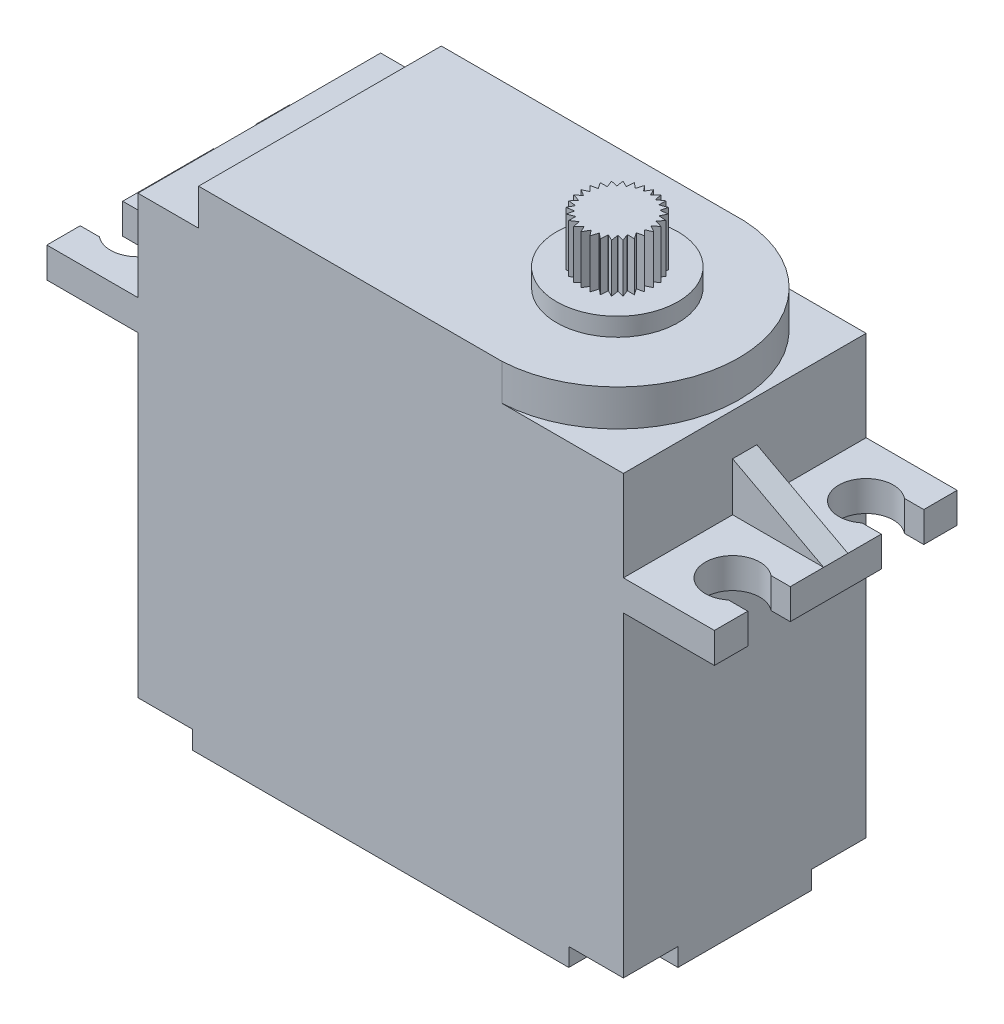
SolidWorks part; units mm, degrees
ref_plane "Front Plane" through (0, 0, 0) normal (0, 0, 1) x (1, 0, 0)
ref_plane "Top Plane" through (0, 0, 0) normal (0, 1, 0) x (1, 0, 0)
ref_plane "Right Plane" through (0, 0, 0) normal (1, 0, 0) x (0, 0, -1)
sketch "Sketch1" plane through (0, 0, 0) normal (0, 1, 0) x (1, 0, 0)
  line L1 (0, 0) -> (40, 0)
  line L2 (0, 0) -> (0, 20)
  line L3 (0, 20) -> (40, 20)
  line L4 (40, 0) -> (40, 20)
  dimension "D1" = 20
  dimension "D2" = 40
extrude "Boss-Extrude1" add sketch "Sketch1" along normal blind 40.5
sketch "Sketch2" plane through (0, 40.5, 0) normal (0, 1, 0) x (1, 0, 0)
  line L0 (40, 0) -> (40, 20) construction
  circle A0 centre (29.5, 10) radius 5
  dimension "D1" = 10.5
extrude "Boss-Extrude2" add sketch "Sketch2" along normal blind 1.5
sketch "Sketch3" plane through (40, 0, 0) normal (1, 0, 0) x (0, 0, -1)
  line L0 (0, 40.5) -> (0, 0) construction
  line L1 (0, 30.05) -> (20, 30.05)
  line L2 (0, 30.05) -> (0, 27.55)
  line L3 (0, 27.55) -> (20, 27.55)
  line L4 (20, 30.05) -> (20, 27.55)
  line L5 (20, 40.5) -> (20, 0) construction
  line L6 (0, 0) -> (20, 0) construction
  dimension "D1" = 27.55
  dimension "D2" = 2.5
extrude "Boss-Extrude3" add sketch "Sketch3" along normal blind 7.5
sketch "Sketch4" plane through (0, 0, 0) normal (-1, 0, 0) x (0, 0, 1)
  line L0 (-20, 40.5) -> (-20, 0) construction
  line L1 (-20, 30.05) -> (0, 30.05)
  line L2 (-20, 30.05) -> (-20, 27.55)
  line L3 (-20, 27.55) -> (0, 27.55)
  line L4 (0, 30.05) -> (0, 27.55)
  line L5 (0, 40.5) -> (0, 0) construction
  line L6 (-20, 0) -> (0, 0) construction
  dimension "D1" = 27.55
  dimension "D2" = 2.5
extrude "Boss-Extrude4" add sketch "Sketch4" along normal blind 7.5
sketch "Sketch5" plane through (0, 40.5, 0) normal (0, 1, 0) x (1, 0, 0)
  line L1 (40, 20) -> (0, 20) construction
  line L2 (5, 20) -> (5, 0)
  line L3 (0, 0) -> (40, 0) construction
  line L5 (5, 20) -> (0, 20)
  line L6 (0, 20) -> (0, 0)
  line L7 (0, 0) -> (5, 0)
  line L8 (30, 0) -> (40, 0)
  line L9 (40, 0) -> (40, 20)
  line L10 (40, 20) -> (30, 20)
  arc A3 (30, 0) -> (30, 20) centre (29.5, 10) ccw
extrude "Cut-Extrude1" cut sketch "Sketch5" against normal blind 3
sketch "Sketch6" plane through (0, 42, 0) normal (0, 1, 0) x (1, 0, 0)
  circle A0 centre (29.5, 10) radius 3
extrude "Boss-Extrude5" add sketch "Sketch6" along normal blind 4
sketch "Sketch7" plane through (0, 46, 0) normal (0, 1, 0) x (1, 0, 0)
  line L0 (29.5, 13) -> (29.1975, 12.4818)
  line L1 (29.5, 13) -> (29.7384, 12.4888)
  line L2 (30.1676, 12.9248) -> (29.7574, 12.4869)
  line L3 (30.1676, 12.9248) -> (30.2863, 12.3733)
  line L4 (30.8017, 12.7029) -> (30.3043, 12.3673)
  line L5 (30.8017, 12.7029) -> (30.7947, 12.1389)
  line L6 (31.3705, 12.3455) -> (30.8109, 12.1289)
  line L7 (31.3705, 12.3455) -> (31.2381, 11.7971)
  line L8 (31.8455, 11.8705) -> (31.2518, 11.7839)
  line L9 (31.8455, 11.8705) -> (31.5945, 11.3653)
  line L10 (32.2029, 11.3017) -> (31.6048, 11.3493)
  line L11 (32.2029, 11.3017) -> (31.8458, 10.865)
  line L12 (32.4248, 10.6676) -> (31.8523, 10.8471)
  line L13 (32.4248, 10.6676) -> (31.9794, 10.3213)
  line L14 (32.5, 10) -> (31.9818, 10.3025)
  line L15 (32.5, 10) -> (31.9888, 9.7616)
  line L16 (32.4248, 9.3324) -> (31.9869, 9.7426)
  line L17 (32.4248, 9.3324) -> (31.8733, 9.2137)
  line L18 (32.2029, 8.6983) -> (31.8673, 9.1957)
  line L19 (32.2029, 8.6983) -> (31.6389, 8.7053)
  line L20 (31.8455, 8.1295) -> (31.6289, 8.6891)
  line L21 (31.8455, 8.1295) -> (31.2971, 8.2619)
  line L22 (31.3705, 7.6545) -> (31.2839, 8.2482)
  line L23 (31.3705, 7.6545) -> (30.8653, 7.9055)
  line L24 (30.8017, 7.2971) -> (30.8493, 7.8952)
  line L25 (30.8017, 7.2971) -> (30.365, 7.6542)
  line L26 (30.1676, 7.0752) -> (30.3471, 7.6477)
  line L27 (30.1676, 7.0752) -> (29.8213, 7.5206)
  line L28 (29.5, 7) -> (29.8025, 7.5182)
  line L29 (29.5, 7) -> (29.2616, 7.5112)
  line L30 (28.8324, 7.0752) -> (29.2426, 7.5131)
  line L31 (28.8324, 7.0752) -> (28.7137, 7.6267)
  line L32 (28.1983, 7.2971) -> (28.6957, 7.6327)
  line L33 (28.1983, 7.2971) -> (28.2053, 7.8611)
  line L34 (27.6295, 7.6545) -> (28.1891, 7.8711)
  line L35 (27.6295, 7.6545) -> (27.7619, 8.2029)
  line L36 (27.1545, 8.1295) -> (27.7482, 8.2161)
  line L37 (27.1545, 8.1295) -> (27.4055, 8.6347)
  line L38 (26.7971, 8.6983) -> (27.3952, 8.6507)
  line L39 (26.7971, 8.6983) -> (27.1542, 9.135)
  line L40 (26.5752, 9.3324) -> (27.1477, 9.1529)
  line L41 (26.5752, 9.3324) -> (27.0206, 9.6787)
  line L42 (26.5, 10) -> (27.0182, 9.6975)
  line L43 (26.5, 10) -> (27.0112, 10.2384)
  line L44 (26.5752, 10.6676) -> (27.0131, 10.2574)
  line L45 (26.5752, 10.6676) -> (27.1267, 10.7863)
  line L46 (26.7971, 11.3017) -> (27.1327, 10.8043)
  line L47 (26.7971, 11.3017) -> (27.3611, 11.2947)
  line L48 (27.1545, 11.8705) -> (27.3711, 11.3109)
  line L49 (27.1545, 11.8705) -> (27.7029, 11.7381)
  line L50 (27.6295, 12.3455) -> (27.7161, 11.7518)
  line L51 (27.6295, 12.3455) -> (28.1347, 12.0945)
  line L52 (28.1983, 12.7029) -> (28.1507, 12.1048)
  line L53 (28.1983, 12.7029) -> (28.635, 12.3458)
  line L54 (28.8324, 12.9248) -> (28.6529, 12.3523)
  line L55 (28.8324, 12.9248) -> (29.1787, 12.4794)
  arc A0 (29.7384, 12.4888) -> (29.1975, 12.4818) centre (29.5, 10) ccw
  circle A1 centre (29.5, 10) radius 3 construction
  circle A2 centre (29.5, 10) radius 3 construction
  arc A3 (30.2863, 12.3733) -> (29.7574, 12.4869) centre (29.5, 10) ccw
  arc A4 (30.7947, 12.1389) -> (30.3043, 12.3673) centre (29.5, 10) ccw
  arc A5 (31.2381, 11.7971) -> (30.8109, 12.1289) centre (29.5, 10) ccw
  arc A6 (31.5945, 11.3653) -> (31.2518, 11.7839) centre (29.5, 10) ccw
  arc A7 (31.8458, 10.865) -> (31.6048, 11.3493) centre (29.5, 10) ccw
  arc A8 (31.9794, 10.3213) -> (31.8523, 10.8471) centre (29.5, 10) ccw
  arc A9 (31.9888, 9.7616) -> (31.9818, 10.3025) centre (29.5, 10) ccw
  arc A10 (31.8733, 9.2137) -> (31.9869, 9.7426) centre (29.5, 10) ccw
  arc A11 (31.6389, 8.7053) -> (31.8673, 9.1957) centre (29.5, 10) ccw
  arc A12 (31.2971, 8.2619) -> (31.6289, 8.6891) centre (29.5, 10) ccw
  arc A13 (30.8653, 7.9055) -> (31.2839, 8.2482) centre (29.5, 10) ccw
  arc A14 (30.365, 7.6542) -> (30.8493, 7.8952) centre (29.5, 10) ccw
  arc A15 (29.8213, 7.5206) -> (30.3471, 7.6477) centre (29.5, 10) ccw
  arc A16 (29.2616, 7.5112) -> (29.8025, 7.5182) centre (29.5, 10) ccw
  arc A17 (28.7137, 7.6267) -> (29.2426, 7.5131) centre (29.5, 10) ccw
  arc A18 (28.2053, 7.8611) -> (28.6957, 7.6327) centre (29.5, 10) ccw
  arc A19 (27.7619, 8.2029) -> (28.1891, 7.8711) centre (29.5, 10) ccw
  arc A20 (27.4055, 8.6347) -> (27.7482, 8.2161) centre (29.5, 10) ccw
  arc A21 (27.1542, 9.135) -> (27.3952, 8.6507) centre (29.5, 10) ccw
  arc A22 (27.0206, 9.6787) -> (27.1477, 9.1529) centre (29.5, 10) ccw
  arc A23 (27.0112, 10.2384) -> (27.0182, 9.6975) centre (29.5, 10) ccw
  arc A24 (27.1267, 10.7863) -> (27.0131, 10.2574) centre (29.5, 10) ccw
  arc A25 (27.3611, 11.2947) -> (27.1327, 10.8043) centre (29.5, 10) ccw
  arc A26 (27.7029, 11.7381) -> (27.3711, 11.3109) centre (29.5, 10) ccw
  arc A27 (28.1347, 12.0945) -> (27.7161, 11.7518) centre (29.5, 10) ccw
  arc A28 (28.635, 12.3458) -> (28.1507, 12.1048) centre (29.5, 10) ccw
  arc A29 (29.1787, 12.4794) -> (28.6529, 12.3523) centre (29.5, 10) ccw
  point P93 (29.5, 10)
  dimension "D1" = 28
extrude "Cut-Extrude2" cut sketch "Sketch7" against normal up to surface (4 mm away) flip side to cut up to face at (29.5, 42, -7)
sketch "Sketch8" plane through (0, 42, 0) normal (0, 1, 0) x (1, 0, 0)
  circle A0 centre (29.5, 10) radius 2.5002
extrude "Boss-Extrude6" add sketch "Sketch8" along normal blind 4
sketch "Sketch9" plane through (0, 30.05, 0) normal (0, 1, 0) x (1, 0, 0)
  line L12 (0, 20) -> (0, 0) construction
  line L13 (0, 11) -> (-7.5, 11)
  line L14 (0, 11) -> (0, 9)
  line L15 (0, 9) -> (-7.5, 9)
  line L16 (-7.5, 11) -> (-7.5, 9)
  line L17 (-7.5, 0) -> (-7.5, 20) construction
  line L18 (0, 0) -> (0, 20) construction
  line L19 (40, 0) -> (40, 20) construction
  line L20 (40, 11) -> (47.5, 11)
  line L21 (40, 11) -> (40, 9)
  line L22 (40, 9) -> (47.5, 9)
  line L23 (47.5, 11) -> (47.5, 9)
  line L24 (47.5, 20) -> (47.5, 0) construction
  point P10 (0, 10)
  dimension "D1" = 1
  dimension "D2" = 2
extrude "Boss-Extrude7" add sketch "Sketch9" along normal blind 4
chamfer "Chamfer1" distance 4 distance2 7.5 1 edges at (-7.5, 34.05, -10) first distance on face at (-7.5, 30.425, -10)
chamfer "Chamfer2" distance 4 distance2 7.5 1 edges at (47.5, 34.05, -10) first distance on face at (47.5, 30.425, -10)
sketch "Sketch10" plane through (0, 30.05, 0) normal (0, 1, 0) x (1, 0, 0)
  line L0 (-7.5, 11) -> (-7.5, 20) construction
  line L1 (47.5, 20) -> (47.5, 11) construction
  line L2 (45.9142, 17.25) -> (47.5, 17.25)
  line L4 (45.9142, 13.75) -> (47.5, 13.75)
  line L5 (47.5, 17.25) -> (47.5, 13.75)
  line L8 (47.5, 9) -> (47.5, 0) construction
  line L9 (45.9142, 2.75) -> (47.5, 2.75)
  line L11 (45.9142, 6.25) -> (47.5, 6.25)
  line L12 (47.5, 2.75) -> (47.5, 6.25)
  line L15 (-7.5, 0) -> (-7.5, 9) construction
  line L16 (-5.9142, 13.75) -> (-7.5, 13.75)
  line L18 (-5.9142, 17.25) -> (-7.5, 17.25)
  line L19 (-7.5, 13.75) -> (-7.5, 17.25)
  line L22 (-5.9142, 2.75) -> (-7.5, 2.75)
  line L24 (-5.9142, 6.25) -> (-7.5, 6.25)
  line L25 (-7.5, 2.75) -> (-7.5, 6.25)
  line L26 (-3.8833, 2.75) -> (-7.5, 6.25) construction
  line L27 (-3.8833, 6.25) -> (-7.5, 2.75) construction
  arc A0 (-5.9142, 13.75) -> (-5.9142, 17.25) centre (-4.5, 15.5) ccw
  arc A1 (45.9142, 17.25) -> (45.9142, 13.75) centre (44.5, 15.5) ccw
  arc A2 (-5.9142, 2.75) -> (-5.9142, 6.25) centre (-4.5, 4.5) ccw
  arc A3 (45.9142, 6.25) -> (45.9142, 2.75) centre (44.5, 4.5) ccw
  point P10 (46.2674, 15.5)
  point P17 (46.2674, 4.5)
  point P24 (-5.6916, 15.5)
  point P29 (-5.6916, 4.5)
  dimension "D1" = 49
  dimension "D2" = 3
extrude "Cut-Extrude3" cut sketch "Sketch10" against normal up to next
sketch "Sketch11" plane through (0, 0, 0) normal (0, -1, 0) x (1, 0, 0)
  line L1 (0, 0) -> (4.5, 0)
  line L2 (0, 0) -> (0, -4.5)
  line L3 (0, -4.5) -> (4.5, -4.5)
  line L4 (4.5, 0) -> (4.5, -4.5)
  line L5 (40, 0) -> (35.5, 0)
  line L6 (40, 0) -> (40, -4.5)
  line L7 (40, -4.5) -> (35.5, -4.5)
  line L8 (35.5, 0) -> (35.5, -4.5)
  line L9 (0, -20) -> (4.5, -20)
  line L10 (0, -20) -> (0, -15.5)
  line L11 (0, -15.5) -> (4.5, -15.5)
  line L12 (4.5, -20) -> (4.5, -15.5)
  line L13 (40, -20) -> (35.5, -20)
  line L14 (40, -20) -> (40, -15.5)
  line L15 (40, -15.5) -> (35.5, -15.5)
  line L16 (35.5, -20) -> (35.5, -15.5)
extrude "Cut-Extrude4" cut sketch "Sketch11" against normal blind 1.5
fillet "Fillet1" radius 2.25 4 edges at (35.5, 0.75, -4.5) (35.5, 0.75, -15.5) (4.5, 0.75, -15.5) (4.5, 0.75, -4.5)
